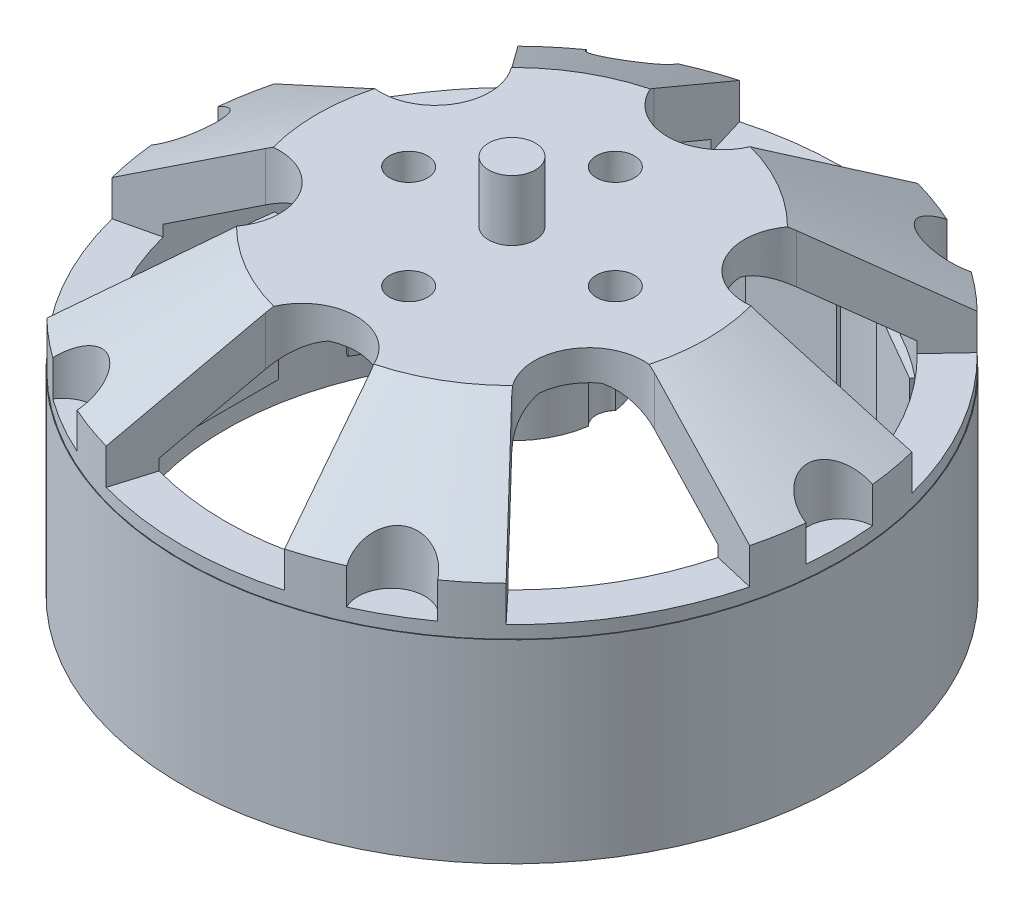
SolidWorks part; units mm, degrees
material "6061-T6 (SS)"
ref_plane "Front Plane" through (0, 0, 0) normal (0, 0, 1) x (1, 0, 0)
ref_plane "Top Plane" through (0, 0, 0) normal (0, 1, 0) x (1, 0, 0)
ref_plane "Right Plane" through (0, 0, 0) normal (1, 0, 0) x (0, 0, -1)
sketch "Sketch2" plane through (0, 0, 0) normal (0, 0, 1) x (1, 0, 0)
  line L0 (0, 0) -> (12.3635, 0)
  line L1 (12.3635, 0) -> (13.7795, 5.1054)
  line L2 (13.7795, 5.1054) -> (13.7795, 6.604)
  line L3 (13.7795, 6.604) -> (11.2395, 6.604)
  line L4 (11.2395, 6.604) -> (11.2395, 7.2136)
  line L5 (11.2395, 7.2136) -> (13.7795, 7.2136)
  line L6 (13.7795, 7.2136) -> (13.7795, 17.3736)
  line L7 (13.7795, 17.3736) -> (8.1597, 20.574)
  line L8 (8.1597, 20.574) -> (0, 20.574)
  line L9 (0, 20.574) -> (0, 0)
  dimension "D1" = 6.604
  dimension "D2" = 20.574
  dimension "D3" = 13.7795
  dimension "D4" = 12.3635
  dimension "D5" = 0.6096
  dimension "D6" = 8.1597
  dimension "D7" = 10.16
  dimension "D8" = 1.4986
  dimension "D9" = 2.54
revolve "Revolve1" add sketch "Sketch2" angle 360 about L9
shell "Shell2" thickness 1.778 removed face at (-8.1597, 20.574, 0)
sketch "Sketch3" plane through (0, 0, 0) normal (0, -1, 0) x (1, 0, 0)
  line L0 (0, 0) -> (-8.7566, 0) construction
  line L1 (0, 0) -> (-8.7423, 8.7423) construction
  line L2 (-8.9295, 4.9961) -> (-6.6644, 2.731) construction
  line L3 (-5.3172, 9.2506) -> (-2.3574, 6.2907) construction
  line L4 (-11.333, 5.01) -> (-14.4659, 7.1019)
  line L5 (-14.4659, 7.1019) -> (-7.293, 14.7521)
  line L6 (-7.293, 14.7521) -> (-5.01, 11.333)
  line L7 (7.1019, 14.4659) -> (14.7521, 7.293)
  line L8 (5.01, 11.333) -> (7.1019, 14.4659)
  line L9 (14.7521, 7.293) -> (11.333, 5.01)
  line L10 (14.4659, -7.1019) -> (7.293, -14.7521)
  line L11 (11.333, -5.01) -> (14.4659, -7.1019)
  line L12 (7.293, -14.7521) -> (5.01, -11.333)
  line L13 (-7.1019, -14.4659) -> (-14.7521, -7.293)
  line L14 (-5.01, -11.333) -> (-7.1019, -14.4659)
  line L15 (-14.7521, -7.293) -> (-11.333, -5.01)
  arc A0 (-8.6482, -1.3742) -> (-8.6482, 1.3742) centre (0, 0) cw construction
  arc A1 (-10.9811, 1.7448) -> (-10.9811, -1.7448) centre (0, 0) ccw
  arc A2 (-6.3152, 1.0035) -> (-6.3152, -1.0035) centre (0, 0) ccw
  arc A3 (-6.3152, 1.0035) -> (-10.9811, 1.7448) centre (-8.6482, 1.3742) ccw
  arc A4 (-10.9811, -1.7448) -> (-6.3152, -1.0035) centre (-8.6482, -1.3742) ccw
  circle A5 centre (0, 0) radius 12.3635 construction
  arc A6 (-1.3742, 8.6482) -> (1.3742, 8.6482) centre (0, 0) cw construction
  arc A7 (1.7448, 10.9811) -> (-1.7448, 10.9811) centre (0, 0) ccw
  arc A8 (1.0035, 6.3152) -> (-1.0035, 6.3152) centre (0, 0) ccw
  arc A9 (1.0035, 6.3152) -> (1.7448, 10.9811) centre (1.3742, 8.6482) ccw
  arc A10 (-1.7448, 10.9811) -> (-1.0035, 6.3152) centre (-1.3742, 8.6482) ccw
  arc A11 (8.6482, 1.3742) -> (8.6482, -1.3742) centre (0, 0) cw construction
  arc A12 (10.9811, -1.7448) -> (10.9811, 1.7448) centre (0, 0) ccw
  arc A13 (6.3152, -1.0035) -> (6.3152, 1.0035) centre (0, 0) ccw
  arc A14 (6.3152, -1.0035) -> (10.9811, -1.7448) centre (8.6482, -1.3742) ccw
  arc A15 (10.9811, 1.7448) -> (6.3152, 1.0035) centre (8.6482, 1.3742) ccw
  arc A16 (1.3742, -8.6482) -> (-1.3742, -8.6482) centre (0, 0) cw construction
  arc A17 (-1.7448, -10.9811) -> (1.7448, -10.9811) centre (0, 0) ccw
  arc A18 (-1.0035, -6.3152) -> (1.0035, -6.3152) centre (0, 0) ccw
  arc A19 (-1.0035, -6.3152) -> (-1.7448, -10.9811) centre (-1.3742, -8.6482) ccw
  arc A20 (1.7448, -10.9811) -> (1.0035, -6.3152) centre (1.3742, -8.6482) ccw
  arc A21 (-10.9496, 5.7411) -> (-5.7411, 10.9496) centre (0, 0) cw construction
  arc A22 (-6.1244, 11.6807) -> (-11.6807, 6.1244) centre (0, 0) ccw
  arc A23 (-5.3578, 10.2185) -> (-10.2185, 5.3578) centre (0, 0) ccw
  arc A24 (-5.3578, 10.2185) -> (-6.1244, 11.6807) centre (-5.7411, 10.9496) ccw
  arc A25 (-11.6807, 6.1244) -> (-10.2185, 5.3578) centre (-10.9496, 5.7411) ccw
  arc A26 (5.7411, 10.9496) -> (10.9496, 5.7411) centre (0, 0) cw construction
  arc A27 (11.6807, 6.1244) -> (6.1244, 11.6807) centre (0, 0) ccw
  arc A28 (10.2185, 5.3578) -> (5.3578, 10.2185) centre (0, 0) ccw
  arc A29 (10.2185, 5.3578) -> (11.6807, 6.1244) centre (10.9496, 5.7411) ccw
  arc A30 (6.1244, 11.6807) -> (5.3578, 10.2185) centre (5.7411, 10.9496) ccw
  arc A31 (10.9496, -5.7411) -> (5.7411, -10.9496) centre (0, 0) cw construction
  arc A32 (6.1244, -11.6807) -> (11.6807, -6.1244) centre (0, 0) ccw
  arc A33 (5.3578, -10.2185) -> (10.2185, -5.3578) centre (0, 0) ccw
  arc A34 (5.3578, -10.2185) -> (6.1244, -11.6807) centre (5.7411, -10.9496) ccw
  arc A35 (11.6807, -6.1244) -> (10.2185, -5.3578) centre (10.9496, -5.7411) ccw
  arc A36 (-5.7411, -10.9496) -> (-10.9496, -5.7411) centre (0, 0) cw construction
  arc A37 (-11.6807, -6.1244) -> (-6.1244, -11.6807) centre (0, 0) ccw
  arc A38 (-10.2185, -5.3578) -> (-5.3578, -10.2185) centre (0, 0) ccw
  arc A39 (-10.2185, -5.3578) -> (-11.6807, -6.1244) centre (-10.9496, -5.7411) ccw
  arc A40 (-6.1244, -11.6807) -> (-5.3578, -10.2185) centre (-5.7411, -10.9496) ccw
  point P4 (-8.7566, 0)
  point P21 (0, 8.7566)
  point P28 (8.7566, 0)
  point P35 (0, -8.7566)
  point P40 (0, 0)
  point P42 (-8.7423, 8.7423)
  point P52 (8.7423, 8.7423)
  point P59 (8.7423, -8.7423)
  point P66 (-8.7423, -8.7423)
  point P71 (0, 0)
  point P88 (0, 0)
  circle M9 centre (0, 0) radius 12.3635
  dimension "D1" = 2.3622
  dimension "D2" = 1.2446
  dimension "D6" = 0.8255
  dimension "D3" = 45
  dimension "D5" = 5.5626
  dimension "D7" = 7.366
  dimension "D4" = 4
  dimension "D8" = 4
  dimension "D9" = 4
extrude "Cut-Extrude1" cut sketch "Sketch3" against normal offset from surface (5.1816 mm away) 1.4224 contours A1 A4 A2 A3 | A7 A10 A8 A9 | A12 A15 A13 A14 | A17 A20 A18 A19 | A37 A40 L14 A39 L15 M9 | A40 A38 A39 M9 | A40 A37 A39 L15 L13 L14 | A25 A22 A24 L6 L5 L4 | A22 A25 L4 A24 L6 M9 | A27 A30 L8 A29 L9 M9 | A30 A28 A29 M9 | A30 A27 A29 L9 L7 L8 | A35 A32 A34 L12 L10 L11 | A23 A25 A22 A24 | A32 A35 A33 A34 region at (-8.8426, 0, 8.8426) region at (-9.9246, 0, 10.0974) region at (-8.8426, 0, -8.8426) region at (-8.2814, 0, -8.2814) region at (8.2814, 0, 8.2814) region at (8.8426, 0, 8.8426) region at (-10.0974, 0, -9.9246) region at (10.0974, 0, 9.9246) region at (9.9246, 0, -10.0974) region at (-8.679, 0, 0) region at (0, 0, 8.679) region at (8.679, 0, 0) region at (0, 0, -8.679) up to face at (-11.2395, 6.604, 0)
sketch "Sketch4" plane through (0, 4.826, 0) normal (0, -1, 0) x (1, 0, 0)
  arc A1 (-10.7821, 4.9328) -> (-10.2185, 5.3578) centre (-10.9496, 5.7411) ccw
  arc A2 (-10.7821, 4.9328) -> (-10.2185, 5.3578) centre (-10.9496, 5.7411) ccw
  arc A18 (-10.7821, 4.9328) -> (-10.7821, -4.9328) centre (0, 0) ccw
  arc A19 (-10.7821, 4.9328) -> (-10.7821, -4.9328) centre (0, 0) ccw
  arc A20 (-10.2185, -5.3578) -> (-10.7821, -4.9328) centre (-10.9496, -5.7411) ccw
  arc A21 (-10.2185, -5.3578) -> (-10.7821, -4.9328) centre (-10.9496, -5.7411) ccw
  arc A22 (-10.2185, -5.3578) -> (-5.3578, -10.2185) centre (0, 0) ccw
  arc A23 (-10.2185, -5.3578) -> (-5.3578, -10.2185) centre (0, 0) ccw
  arc A24 (-4.9328, -10.7821) -> (-5.3578, -10.2185) centre (-5.7411, -10.9496) ccw
  arc A25 (-4.9328, -10.7821) -> (-5.3578, -10.2185) centre (-5.7411, -10.9496) ccw
  arc A26 (-4.9328, -10.7821) -> (4.9328, -10.7821) centre (0, 0) ccw
  arc A27 (-4.9328, -10.7821) -> (4.9328, -10.7821) centre (0, 0) ccw
  arc A28 (5.3578, -10.2185) -> (4.9328, -10.7821) centre (5.7411, -10.9496) ccw
  arc A29 (5.3578, -10.2185) -> (4.9328, -10.7821) centre (5.7411, -10.9496) ccw
  arc A30 (5.3578, -10.2185) -> (10.2185, -5.3578) centre (0, 0) ccw
  arc A31 (5.3578, -10.2185) -> (10.2185, -5.3578) centre (0, 0) ccw
  arc A32 (10.7821, -4.9328) -> (10.2185, -5.3578) centre (10.9496, -5.7411) ccw
  arc A33 (10.7821, -4.9328) -> (10.2185, -5.3578) centre (10.9496, -5.7411) ccw
  arc A34 (10.7821, -4.9328) -> (10.7821, 4.9328) centre (0, 0) ccw
  arc A35 (10.7821, -4.9328) -> (10.7821, 4.9328) centre (0, 0) ccw
  arc A36 (10.2185, 5.3578) -> (10.7821, 4.9328) centre (10.9496, 5.7411) ccw
  arc A37 (10.2185, 5.3578) -> (10.7821, 4.9328) centre (10.9496, 5.7411) ccw
  arc A38 (10.2185, 5.3578) -> (5.3578, 10.2185) centre (0, 0) ccw
  arc A39 (10.2185, 5.3578) -> (5.3578, 10.2185) centre (0, 0) ccw
  arc A40 (4.9328, 10.7821) -> (5.3578, 10.2185) centre (5.7411, 10.9496) ccw
  arc A41 (4.9328, 10.7821) -> (5.3578, 10.2185) centre (5.7411, 10.9496) ccw
  arc A42 (4.9328, 10.7821) -> (-4.9328, 10.7821) centre (0, 0) ccw
  arc A43 (4.9328, 10.7821) -> (-4.9328, 10.7821) centre (0, 0) ccw
  arc A44 (-5.3578, 10.2185) -> (-4.9328, 10.7821) centre (-5.7411, 10.9496) ccw
  arc A45 (-5.3578, 10.2185) -> (-4.9328, 10.7821) centre (-5.7411, 10.9496) ccw
  arc A46 (-5.3578, 10.2185) -> (-10.2185, 5.3578) centre (0, 0) ccw
  arc A47 (-5.3578, 10.2185) -> (-10.2185, 5.3578) centre (0, 0) ccw
  dimension "D1" = 0
extrude "Cut-Extrude2" cut sketch "Sketch4" against normal up to next
sketch "Sketch6" plane through (0, 20.574, 0) normal (0, 1, 0) x (1, 0, 0)
  circle A0 centre (0, 0) radius 8.1597 construction
  circle A1 centre (0, 0) radius 8.1597
extrude "Boss-Extrude4" add sketch "Sketch6" against normal blind 1.27
sketch "Sketch7" plane through (0, 20.574, 0) normal (0, 1, 0) x (1, 0, 0)
  line L0 (-2.1885, 8.1405) -> (-3.8907, 13.7795)
  line L1 (-3.8907, 13.7795) -> (3.8907, 13.7795)
  line L2 (3.8907, 13.7795) -> (2.1885, 8.1405)
  line L3 (0, 0) -> (0, 13.7795) construction
  line L4 (5.9556, 5.9655) -> (9.9881, 10.2592)
  line L5 (9.9881, 10.2592) -> (13.8787, 3.5203)
  line L6 (13.8787, 3.5203) -> (8.1441, 2.175)
  line L7 (8.1441, -2.175) -> (13.8787, -3.5203)
  line L8 (13.8787, -3.5203) -> (9.9881, -10.2592)
  line L9 (9.9881, -10.2592) -> (5.9556, -5.9655)
  line L10 (2.1885, -8.1405) -> (3.8907, -13.7795)
  line L11 (3.8907, -13.7795) -> (-3.8907, -13.7795)
  line L12 (-3.8907, -13.7795) -> (-2.1885, -8.1405)
  line L13 (-5.9556, -5.9655) -> (-9.9881, -10.2592)
  line L14 (-9.9881, -10.2592) -> (-13.8787, -3.5203)
  line L15 (-13.8787, -3.5203) -> (-8.1441, -2.175)
  line L16 (-8.1441, 2.175) -> (-13.8787, 3.5203)
  line L17 (-13.8787, 3.5203) -> (-9.9881, 10.2592)
  line L18 (-9.9881, 10.2592) -> (-5.9556, 5.9655)
  line L19 (0, 0) -> (6.8898, 11.9334) construction
  arc A0 (-2.1885, 8.1405) -> (2.1885, 8.1405) centre (0, 8.8011) ccw
  arc A2 (5.9556, 5.9655) -> (8.1441, 2.175) centre (7.622, 4.4006) ccw
  arc A3 (8.1441, -2.175) -> (5.9556, -5.9655) centre (7.622, -4.4005) ccw
  arc A4 (2.1885, -8.1405) -> (-2.1885, -8.1405) centre (0, -8.8011) ccw
  arc A5 (-5.9556, -5.9655) -> (-8.1441, -2.175) centre (-7.622, -4.4006) ccw
  arc A6 (-8.1441, 2.175) -> (-5.9556, 5.9655) centre (-7.622, 4.4005) ccw
  circle A7 centre (0, 0) radius 13.7795 construction
  circle A8 centre (0, 0) radius 6.5151 construction
  circle A9 centre (6.8898, 11.9334) radius 1.397
  circle A10 centre (13.7795, 0) radius 1.397
  circle A11 centre (6.8897, -11.9334) radius 1.397
  circle A12 centre (-6.8898, -11.9334) radius 1.397
  circle A13 centre (-13.7795, 0) radius 1.397
  circle A14 centre (-6.8897, 11.9334) radius 1.397
  point P1 (3.735, 13.2637)
  point P11 (9.6192, 9.8664)
  point P38 (0, 0)
  point P53 (0, 0)
  dimension "D1" = 4.572
  dimension "D4" = 13.0302
  dimension "D5" = 2.794
  dimension "D2" = 6
  dimension "D3" = 6.7945
  dimension "D6" = 30
  dimension "D7" = 6
extrude "Cut-Extrude3" cut sketch "Sketch7" against normal blind 4.699
sketch "Sketch20" plane through (0, 19.304, 0) normal (0, -1, 0) x (1, 0, 0)
  circle A0 centre (0, 0) radius 3.81
  arc A1 (0.9639, -6.7283) -> (5.3449, -4.1989) centre (0, 0) ccw construction
  dimension "D1" = 7.62
extrude "Boss-Extrude9" add sketch "Sketch20" along normal blind 3.81
hole_wizard "M2 Tapped Hole1" positions "Sketch11" profile "Sketch12" tap size "M2" standard "ISO" end condition through all
sketch "Sketch11" plane through (0, 20.574, 0) normal (0, 1, 0) x (1, 0, 0)
  line L1 (-4.3285, 0) -> (0, -4.3285) construction
  line L2 (0, -4.3285) -> (4.3285, 0) construction
  line L3 (4.3285, 0) -> (0, 4.3285) construction
  line L5 (0, 4.3285) -> (-4.3285, 0) construction
  line L8 (4.3285, 0) -> (-4.3285, 0) construction
  line L10 (0, 4.3285) -> (0, -4.3285) construction
  line L11 (0, -6.5151) -> (0, 6.5151) construction
  line L13 (-8.1598, 0) -> (8.1598, 0) construction
  arc A0 (2.095, -7.8862) -> (-2.095, -7.8862) centre (0, -8.8011) ccw construction
  arc A1 (-2.095, 7.8862) -> (2.095, 7.8862) centre (0, 8.8011) ccw construction
  arc A2 (-7.8772, 2.1288) -> (-7.8772, -2.1288) centre (0, 0) ccw construction
  arc A3 (7.8772, -2.1288) -> (7.8772, 2.1288) centre (0, 0) ccw construction
  point P0 (0, 4.3285)
  point P2 (4.3285, 0)
  point P4 (0, -4.3285)
  point P6 (-4.3285, 0)
  dimension "D1" = 6.1214
cosmetic thread "Hole Thread5" parameters "D2"=2
cosmetic thread "Hole Thread6" parameters "D2"=2
cosmetic thread "Hole Thread7" parameters "D2"=2
cosmetic thread "Hole Thread8" parameters "D2"=2
sketch "Sketch12" plane through (0, 20.574, -4.3285) normal (1, 0, 0) x (0, 0, 1)
  line L0 (0, 0) -> (0, 20.574)
  line L1 (0, 20.574) -> (0.8, 20.574)
  line L2 (0.8, 20.574) -> (0.8, 0)
  line L5 (0.8, 0) -> (0, 0)
  line L11 (0, -6.35) -> (0, 107.95) construction
  dimension "Thru Tap Drill Dia." = 1.6
  dimension "Thru Tap Drill Depth" = 20.574
sketch "Sketch13" plane through (0, 20.574, 0) normal (0, 1, 0) x (1, 0, 0)
  circle A0 centre (0, 0) radius 0.9779
  dimension "D1" = 1.9558
extrude "Boss-Extrude5" add sketch "Sketch13" along normal blind 2.54
sketch "Sketch16" plane through (0, 0, 0) normal (0, 1, 0) x (1, 0, 0)
  circle A0 centre (0, 0) radius 22.4802
extrude "Cut-Extrude4" cut sketch "Sketch16" along normal up to surface (7.2136 mm away) up to face at (0, 7.2136, 0)
sketch "Sketch17" plane through (0, 7.2136, 0) normal (0, -1, 0) x (1, 0, 0)
  circle A0 centre (0, 0) radius 12.0015 construction
  circle A1 centre (0, 0) radius 12.0015
extrude "Cut-Extrude5" cut sketch "Sketch17" against normal up to next (8.2804 mm away)
sketch "Sketch18" plane through (0, 0, 0) normal (0, 0, 1) x (1, 0, 0)
  line L1 (1.905, 8.2296) -> (-1.905, 8.2296)
  line L2 (1.905, 8.2296) -> (1.905, 14.224)
  line L3 (1.905, 14.224) -> (-1.905, 14.224)
  line L4 (-1.905, 8.2296) -> (-1.905, 14.224)
  line L5 (1.905, 8.2296) -> (-1.905, 14.224) construction
  line L6 (1.905, 14.224) -> (-1.905, 8.2296) construction
  line L7 (3.735, 15.875) -> (-3.735, 15.875) construction
  line L9 (-12.0015, 7.2136) -> (12.0015, 7.2136) construction
  point P4 (0, 11.2268)
  dimension "D1" = 1.651
  dimension "D2" = 3.81
  dimension "D3" = 1.016
extrude "Boss-Extrude8" add sketch "Sketch18" along normal up to surface (0.1653 mm away) from offset 11.684
sketch "Sketch19" plane through (0, 0, 0) normal (0, 0, 1) x (1, 0, 0)
  line L0 (-13.7795, 15.875) -> (-13.7795, 7.2136) construction
  line L1 (-13.7795, 15.3416) -> (-13.8049, 15.3416)
  line L2 (-13.7795, 15.3416) -> (-13.7795, 7.2136)
  line L3 (-13.7795, 7.2136) -> (-13.8049, 7.2136)
  line L4 (-13.8049, 15.3416) -> (-13.8049, 7.2136)
  line L5 (-13.7795, 15.3416) -> (-13.8049, 7.2136) construction
  line L6 (-13.7795, 7.2136) -> (-13.8049, 15.3416) construction
  line L7 (-13.7795, 7.2136) -> (13.7795, 7.2136) construction
  point P4 (-13.7922, 11.2776)
  dimension "D1" = 8.128
  dimension "D2" = 0.0254
ref_axis "Axis1" through (0, 8.9916, 0) along (0, 1, 0)
revolve "Revolve2" add sketch "Sketch19" angle 360 about axis through (0, 8.9916, 0) along (0, 1, 0)
pattern_circular "CirPattern1" count 12 every 30 about axis through (0, 8.9916, 0) along (0, 1, 0) of "Boss-Extrude8"
